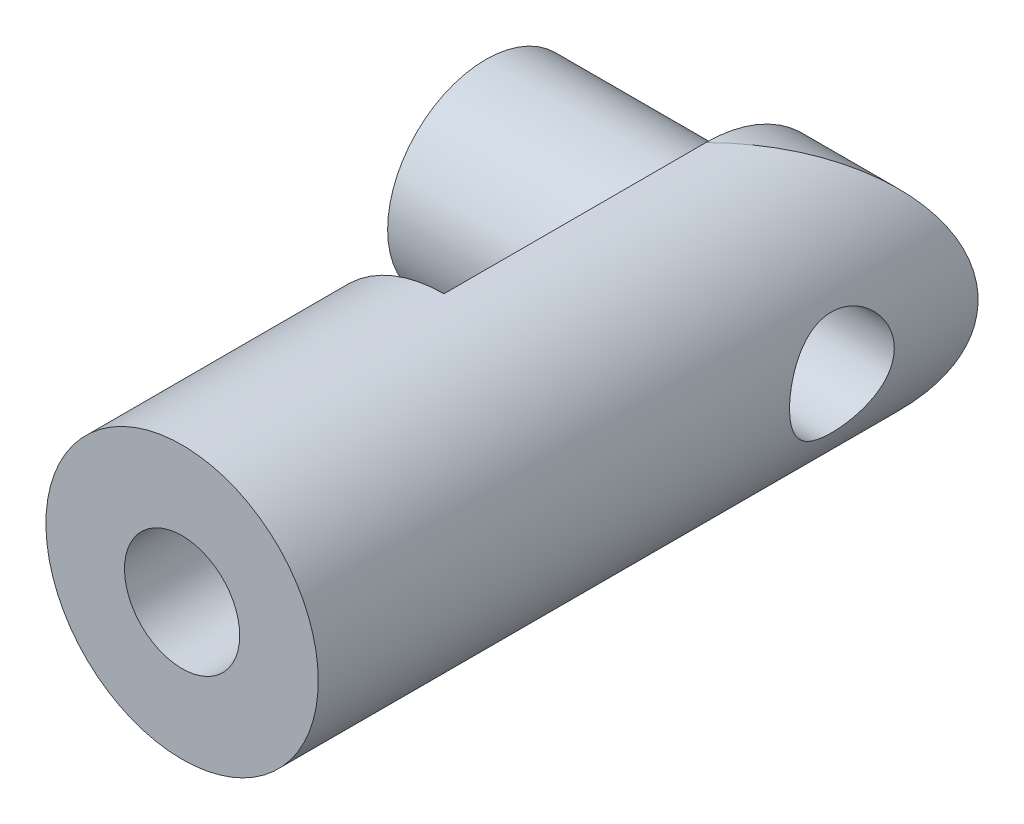
SolidWorks part; units mm, degrees
ref_plane "Front Plane" through (0, 0, 0) normal (0, 0, 1) x (1, 0, 0)
ref_plane "Top Plane" through (0, 0, 0) normal (0, 1, 0) x (1, 0, 0)
ref_plane "Right Plane" through (0, 0, 0) normal (1, 0, 0) x (0, 0, -1)
sketch "Sketch8" plane through (0, 0, 0) normal (0, 0, 1) x (1, 0, 0)
  circle A0 centre (0, 0) radius 1.1
  circle A1 centre (0, 0) radius 2.6
  dimension "D1" = 2.2
  dimension "D2" = 1.5
extrude "Boss-Extrude2" add sketch "Sketch8" along normal blind 5
sketch "Sketch9" plane through (0, 0, 0) normal (1, 0, 0) x (0, 0, -1)
  line L0 (0, 2.6) -> (5, 2.6)
  line L1 (0, -2.6) -> (5, -2.6)
  line L2 (0, 2.6) -> (0, -2.6)
  arc A0 (5, 2.6) -> (5, -2.6) centre (5, 0) cw
  dimension "D1" = 5
extrude "Boss-Extrude3" add sketch "Sketch9" along normal up to surface up to face at (2.6, 0, 5)
sketch "Sketch10" plane through (0, 0, 0) normal (-1, 0, 0) x (0, 0, 1)
  circle A0 centre (-5, 0) radius 1.875
  dimension "D1" = 3.75
extrude "Boss-Extrude4" add sketch "Sketch10" along normal blind 4.2
sketch "Sketch11" plane through (-4.2, 0, 0) normal (-1, 0, 0) x (0, 0, 1)
  circle A0 centre (-5, 0) radius 1
  dimension "D1" = 2
extrude "Cut-Extrude1" cut sketch "Sketch11" against normal through all
